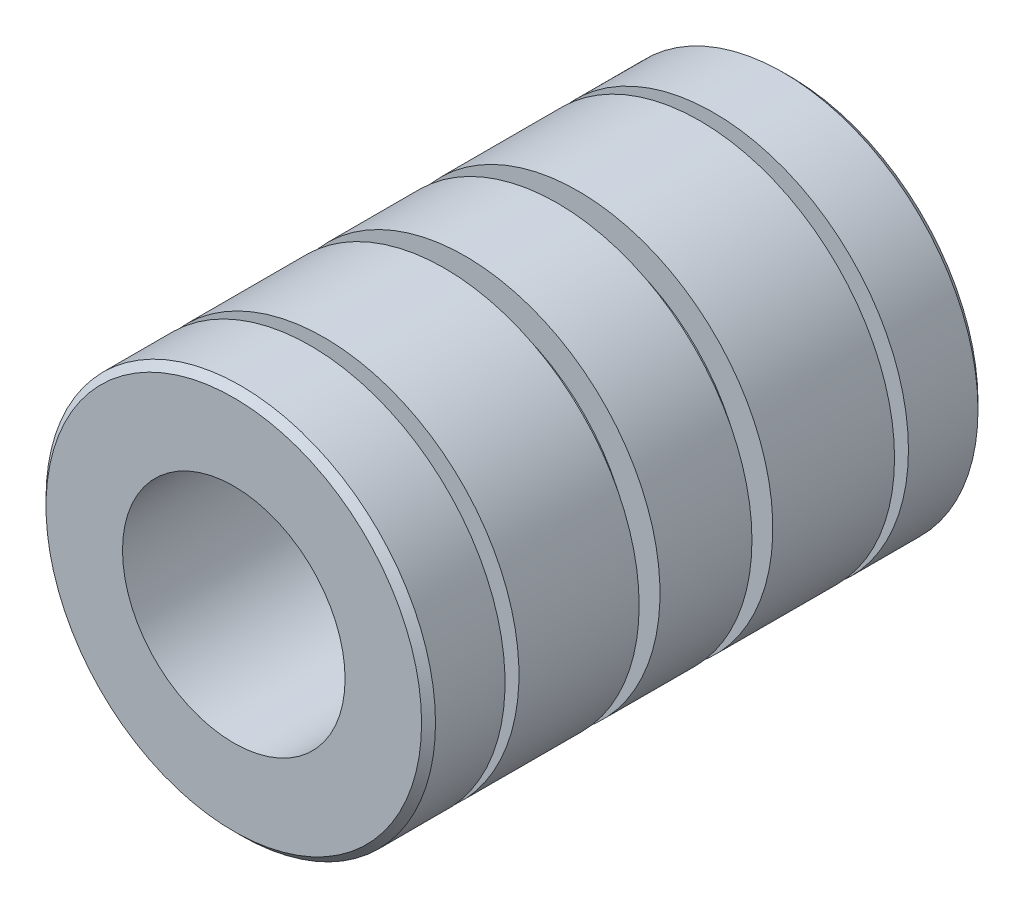
SolidWorks part; units mm, degrees
ref_plane "Front Plane" through (0, 0, 0) normal (0, 0, 1) x (1, 0, 0)
ref_plane "Top Plane" through (0, 0, 0) normal (0, 1, 0) x (1, 0, 0)
ref_plane "Right Plane" through (0, 0, 0) normal (1, 0, 0) x (0, 0, -1)
sketch "Sketch2" plane through (0, 0, 0) normal (0, 0, 1) x (1, 0, 0)
  circle A0 centre (0, 0) radius 11.1125
  dimension "D1" = 22.225
extrude "Boss-Extrude1" add sketch "Sketch2" along normal blind 31.75
sketch "Sketch3" plane through (0, 0, 31.75) normal (0, 0, 1) x (1, 0, 0)
  circle A0 centre (0, 0) radius 6.35
  dimension "D1" = 12.7
extrude "Cut-Extrude1" cut sketch "Sketch3" against normal through all
sketch "Sketch4" plane through (0, 0, 0) normal (0, 1, 0) x (1, 0, 0)
  line L3 (12.7, -26.5906) -> (9.525, -26.5906)
  line L4 (12.7, -26.5906) -> (12.7, -27.3844)
  line L5 (12.7, -27.3844) -> (9.525, -27.3844)
  line L6 (9.525, -26.5906) -> (9.525, -27.3844)
  line L7 (12.7, -26.5906) -> (9.525, -27.3844) construction
  line L8 (12.7, -27.3844) -> (9.525, -26.5906) construction
  line L10 (9.525, -4.3656) -> (12.7, -4.3656)
  line L11 (9.525, -4.3656) -> (9.525, -5.1594)
  line L12 (9.525, -5.1594) -> (12.7, -5.1594)
  line L13 (12.7, -4.3656) -> (12.7, -5.1594)
  line L14 (9.525, -4.3656) -> (12.7, -5.1594) construction
  line L15 (9.525, -5.1594) -> (12.7, -4.3656) construction
revolve "Cut-Revolve1" cut sketch "Sketch4" angle 360 about axis through (0, 0, 31.75) along (0, 0, -1)
sketch "Sketch5" plane through (0, 0, 0) normal (0, 1, 0) x (1, 0, 0)
  line L0 (11.1125, -26.5906) -> (11.1125, -5.1594) construction
  line L1 (9.525, -12.1047) -> (12.7, -12.1047)
  line L2 (9.525, -12.1047) -> (9.525, -13.2953)
  line L3 (9.525, -13.2953) -> (12.7, -13.2953)
  line L4 (12.7, -12.1047) -> (12.7, -13.2953)
  line L5 (9.525, -12.1047) -> (12.7, -13.2953) construction
  line L6 (9.525, -13.2953) -> (12.7, -12.1047) construction
  line L8 (9.525, -19.7331) -> (12.7, -19.7331)
  line L9 (9.525, -19.7331) -> (9.525, -18.5425)
  line L10 (9.525, -18.5425) -> (12.7, -18.5425)
  line L11 (12.7, -19.7331) -> (12.7, -18.5425)
  line L12 (9.525, -19.7331) -> (12.7, -18.5425) construction
  line L13 (9.525, -18.5425) -> (12.7, -19.7331) construction
  point P0 (11.1125, -12.7)
  point P7 (11.1125, -19.1378)
chamfer "Chamfer1" distance 0.3969 angle 45 2 edges at (11.1125, 0, 0) (11.1125, 0, 31.75)
revolve "Cut-Revolve2" cut sketch "Sketch5" angle 360 about axis through (0, 0, 31.75) along (0, 0, -1)
